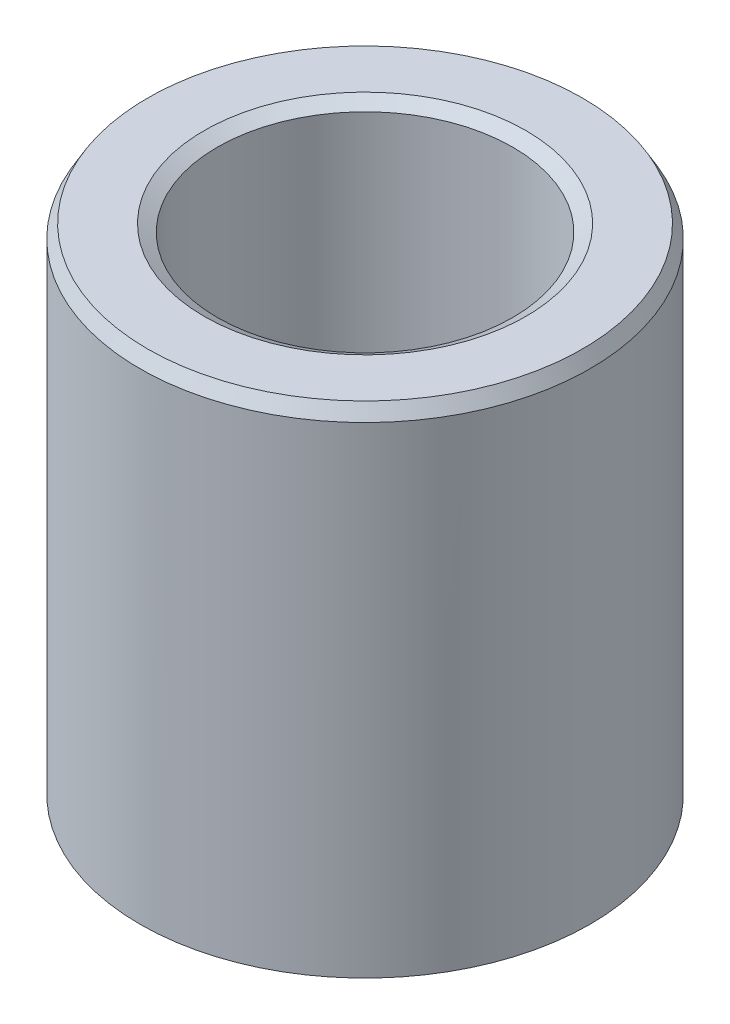
SolidWorks part; units mm, degrees
ref_plane "Front Plane" through (0, 0, 0) normal (0, 0, 1) x (1, 0, 0)
ref_plane "Top Plane" through (0, 0, 0) normal (0, 1, 0) x (1, 0, 0)
ref_plane "Right Plane" through (0, 0, 0) normal (1, 0, 0) x (0, 0, -1)
sketch "Sketch1" plane through (0, 0, 0) normal (0, 1, 0) x (1, 0, 0)
  circle A0 centre (0, 0) radius 15
  dimension "SLEEVE_OD" = 30
extrude "Boss-Extrude1" add sketch "Sketch1" along normal blind 33.4597
sketch "Sketch2" plane through (0, 0, 0) normal (0, 1, 0) x (1, 0, 0)
  circle A0 centre (0, 0) radius 9.8409
  dimension "BORE_D" = 19.6817
extrude "Cut-Extrude1" cut sketch "Sketch2" along normal through all
chamfer "Chamfer1" distance 0.8846 angle 30 4 edges at (0, 33.4597, 9.8409) (0, 0, 9.8409) (0, 0, 15) (0, 33.4597, 15) first distance on face at (0, 33.4597, 9.8409) first distance on face at (0, 0, 9.8409) first distance on face at (0, 33.4597, 15)
